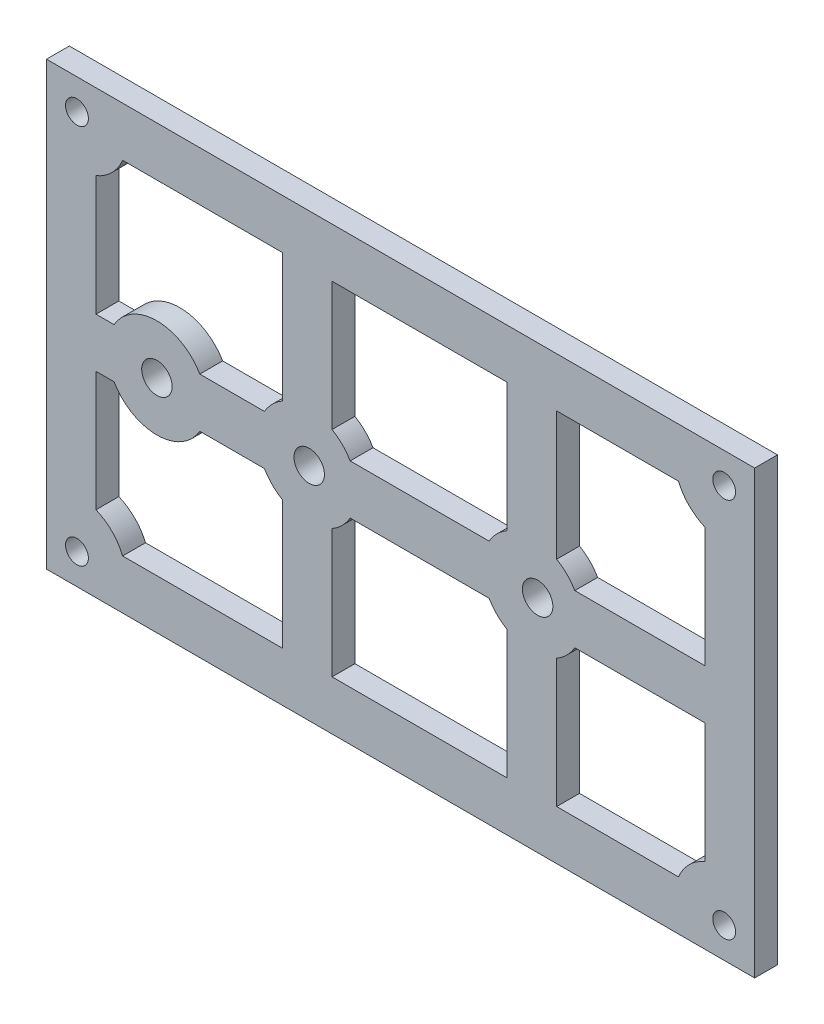
SolidWorks part; units mm, degrees
ref_plane "Front Plane" through (0, 0, 0) normal (0, 0, 1) x (1, 0, 0)
ref_plane "Top Plane" through (0, 0, 0) normal (0, 1, 0) x (1, 0, 0)
ref_plane "Right Plane" through (0, 0, 0) normal (1, 0, 0) x (0, 0, -1)
sketch "Sketch1" plane through (0, 0, 0) normal (0, 0, 1) x (1, 0, 0)
  line L1 (-46.5, 29) -> (46.5, 29)
  line L2 (-46.5, 29) -> (-46.5, -29)
  line L3 (-46.5, -29) -> (46.5, -29)
  line L4 (46.5, 29) -> (46.5, -29)
  line L5 (-46.5, 29) -> (46.5, -29) construction
  line L6 (-46.5, -29) -> (46.5, 29) construction
  point P0 (0, 0)
  dimension "D1" = 93
  dimension "D2" = 58
extrude "Boss-Extrude1" add sketch "Sketch1" along normal blind 3
sketch "Sketch2" plane through (0, 0, 3) normal (0, 0, 1) x (1, 0, 0)
  line L0 (-46.5, 29) -> (-46.5, 25)
  line L1 (-46.5, 29) -> (-46.5, -29) construction
  line L2 (-46.5, 29) -> (-42.5, 29)
  line L3 (46.5, 29) -> (-46.5, 29) construction
  line L4 (-42.5, 29) -> (-42.5, 25)
  line L5 (-42.5, 25) -> (-46.5, 25)
  line L6 (0, 0) -> (46.5, 0) construction
  line L7 (46.5, -29) -> (46.5, 29) construction
  line L8 (0, 0) -> (0, 29) construction
  circle A0 centre (-42.5, 25) radius 1.5
  circle A1 centre (-42.5, -25) radius 1.5
  circle A2 centre (42.5, 25) radius 1.5
  circle A3 centre (42.5, -25) radius 1.5
  dimension "D1" = 3
  dimension "D2" = 4
extrude "Cut-Extrude2" cut sketch "Sketch2" against normal blind 3 contours L5 A0 L4 | L4 A0 L5 | A1 | A3 | A2 region at (-43.1366, 25.6366, 3) region at (-42.2878, 24.7878, 3) region at (-42.5, -25, 3)
sketch "Sketch5" plane through (0, 0, 3) normal (0, 0, 1) x (1, 0, 0)
  line L0 (46.5, 29) -> (-46.5, 29) construction
  line L1 (-40, 22.5) -> (-40, -22.5)
  line L2 (-46.5, -29) -> (46.5, -29) construction
  line L3 (-46.5, 29) -> (-46.5, -29) construction
  line L4 (-33.5, -22.5) -> (-33.5, 22.5)
  line L5 (-33.5, 22.5) -> (-33.5, -22.5)
  line L6 (-33.5, 22.5) -> (-27, 22.5)
  line L7 (-33.5, -22.5) -> (-27, -22.5)
  line L8 (-46.5, 19.8765) -> (-46.5, 29)
  line L9 (-27, 22.5) -> (-27, -22.5)
  line L10 (-27, -22.5) -> (-22, -22.5)
  line L11 (-46.5, 29) -> (-37.3765, 29)
  line L12 (-33.5, 22.5) -> (-40, 22.5)
  line L13 (-33.5, -22.5) -> (-40, -22.5)
  line L14 (-22, -22.5) -> (-22, 22.5)
  line L15 (-22, 22.5) -> (-27, 22.5)
  line L16 (0, 0) -> (0, 29) construction
  line L17 (27, -22.5) -> (20.5, -22.5)
  line L18 (20.5, -22.5) -> (20.5, 22.5)
  line L19 (20.5, 22.5) -> (27, 22.5)
  line L20 (33.5, 22.5) -> (27, 22.5)
  line L21 (27, 22.5) -> (27, -22.5)
  line L22 (33.5, -22.5) -> (27, -22.5)
  line L23 (33.5, 22.5) -> (33.5, -22.5)
  line L24 (33.5, 22.5) -> (40, 22.5)
  line L25 (33.5, -22.5) -> (33.5, 22.5)
  line L26 (33.5, -22.5) -> (40, -22.5)
  line L27 (40, 22.5) -> (40, -22.5)
  line L28 (46.5, 19.8765) -> (46.5, 29)
  line L29 (46.5, 29) -> (37.3765, 29)
  line L30 (0, 0) -> (46.5, 0) construction
  line L31 (46.5, -29) -> (46.5, 29) construction
  line L32 (46.5, -29) -> (37.3765, -29)
  line L33 (46.5, -19.8765) -> (46.5, -29)
  line L34 (-46.5, -19.8765) -> (-46.5, -29)
  line L35 (-46.5, -29) -> (-37.3765, -29)
  line L36 (27, -22.5) -> (27, 22.5)
  line L37 (-22, 22.5) -> (-15.5, 22.5)
  line L38 (-15.5, 22.5) -> (-15.5, -22.5)
  line L39 (-15.5, -22.5) -> (-22, -22.5)
  arc A0 (46.5, 19.8765) -> (37.3765, 29) centre (42.5, 25) cw
  arc A1 (-46.5, 19.8765) -> (-37.3765, 29) centre (-42.5, 25) ccw
  arc A2 (46.5, -19.8765) -> (37.3765, -29) centre (42.5, -25) ccw
  arc A3 (-46.5, -19.8765) -> (-37.3765, -29) centre (-42.5, -25) cw
  dimension "D3" = 6.5
  dimension "D1" = 6.5
  dimension "D2" = 6.5
  dimension "D4" = 6.5
  dimension "D5" = 6.5
  dimension "D6" = 6.5
  dimension "D7" = 5
  dimension "D8" = 6.5
extrude "Cut-Extrude3" cut sketch "Sketch5" against normal blind 10 and the other way blind 10 contours A1 L1 L13 L4 L12 | L9 L6 L4 L7 | L14 L15 L9 L10 | L21 | L23 L20 L21 L22 | A2 L27 A0 L24 L23 L26 | L39 L38 L37 L14 region at (-36.6419, 0, 3) region at (-30.25, 0, 3) region at (-24.5, 0, 3) region at (-18.75, 0, 3) region at (23.75, 0, 3) region at (30.25, 0, 3) region at (36.6419, 0, 3)
sketch "Sketch6" plane through (0, 0, 3) normal (0, 0, 1) x (1, 0, 0)
  line L5 (14, 22.5) -> (14, -22.5)
  line L9 (14, 22.5) -> (-9, 22.5)
  line L10 (2.5, 22.5) -> (2.5, -22.5) construction
  line L15 (-9, 22.5) -> (-9, -22.5)
  line L16 (-9, -22.5) -> (14, -22.5)
  line L17 (20.5, 22.5) -> (20.5, -22.5) construction
  line L18 (46.5, 29) -> (-46.5, 29) construction
  line L19 (-46.5, -29) -> (46.5, -29) construction
  line L21 (-8.4702, 22.5) -> (-9, 22.5)
  line L22 (-9, -22.5) -> (-8.4702, -22.5)
  line L25 (-15.5, -22.5) -> (-15.5, 22.5) construction
  dimension "D1" = 6.5
  dimension "D2" = 45
  dimension "D3" = 6.5
  dimension "D7" = 6.5
  dimension "D8" = 6.5
extrude "Cut-Extrude4" cut sketch "Sketch6" against normal blind 10 contours L5 | L5 L16 L15 L9 region at (2.5, 0, 3)
sketch "Sketch7" plane through (0, 0, 3) normal (0, 0, 1) x (1, 0, 0)
  line L0 (-46.5, -3.25) -> (46.5, -3.25)
  line L1 (-46.5, 29) -> (-46.5, -29) construction
  line L2 (46.5, -29) -> (46.5, 29) construction
  line L3 (-46.5, 3.25) -> (46.5, 3.25)
  line L4 (-46.5, -3.25) -> (-46.5, 3.25)
  line L5 (46.5, 3.25) -> (46.5, -3.25)
  line L6 (-46.5, 0) -> (46.5, 0) construction
  dimension "D1" = 6.5
extrude "Boss-Extrude2" add sketch "Sketch7" against normal through all
sketch "Sketch8" plane through (0, 0, 3) normal (0, 0, 1) x (1, 0, 0)
  line L0 (0, 0) -> (0, 29) construction
  line L5 (-15.5, -3.25) -> (-15.5, 3.25)
  line L6 (-15.5, 3.25) -> (-9, 3.25)
  line L7 (46.5, 29) -> (-46.5, 29) construction
  line L8 (-9, 3.25) -> (-9, -3.25)
  line L9 (-9, -3.25) -> (-15.5, -3.25)
  line L10 (2.5, -22.5) -> (2.5, 22.5) construction
  line L11 (-9, -22.5) -> (14, -22.5) construction
  line L12 (14, 22.5) -> (-9, 22.5) construction
  line L13 (20.5, 3.25) -> (14, 3.25)
  line L14 (14, 3.25) -> (14, -3.25)
  line L15 (20.5, -3.25) -> (20.5, 3.25)
  line L16 (14, -3.25) -> (20.5, -3.25)
  circle A1 centre (-12.25, 0) radius 6.5
  circle A2 centre (17.25, 0) radius 6.5
  point P29 (-12.25, 0)
extrude "Boss-Extrude3" add sketch "Sketch8" against normal through all
sketch "Sketch9" plane through (0, 0, 3) normal (0, 0, 1) x (1, 0, 0)
  line L0 (-46.5, 0) -> (46.5, 0) construction
  line L1 (-46.5, 29) -> (-46.5, -29) construction
  line L2 (46.5, -29) -> (46.5, 29) construction
  line L5 (-9, -22.5) -> (-12.25, -22.472) construction
  line L6 (-12.25, -22.472) -> (-12.001, 6.455) construction
  circle A2 centre (-12.001, 0) radius 2
  circle A4 centre (17.999, 0) radius 2
  dimension "D1" = 4
  dimension "D2" = 4
  dimension "D3" = 30
extrude "Cut-Extrude6" cut sketch "Sketch9" against normal through all
sketch "Sketch12" plane through (0, 0, 3) normal (0, 0, 1) x (1, 0, 0)
  line L2 (-46.5, 29) -> (-46.5, -29) construction
  circle A3 centre (-32, 0) radius 6.5
  circle A4 centre (-32, 0) radius 2
  point P2 (-39.7514, 0)
  point P5 (0, 0)
  dimension "D1" = 13
  dimension "D2" = 4
  dimension "D3" = 14.5
extrude "Boss-Extrude5" add sketch "Sketch12" against normal through all
sketch "Sketch13" plane through (0, 0, 3) normal (0, 0, 1) x (1, 0, 0)
  circle A0 centre (-32.001, 0) radius 5
  circle A1 centre (-12.001, 0) radius 15
  circle A2 centre (-12.001, 0) radius 7.5
  circle A3 centre (17.999, 0) radius 22.5
  circle A4 centre (-12.001, 0) radius 2 construction
  dimension "D1" = 10
  dimension "D2" = 30
  dimension "D3" = 15
  dimension "D4" = 45
  dimension "D5" = 30
sketch "Sketch14" plane through (0, 0, 3) normal (0, 0, 1) x (1, 0, 0)
  circle A0 centre (-32.001, 0) radius 2
  point P4 (-40, 0)
  dimension "D1" = 4
extrude "Cut-Extrude7" cut sketch "Sketch14" against normal blind 10
